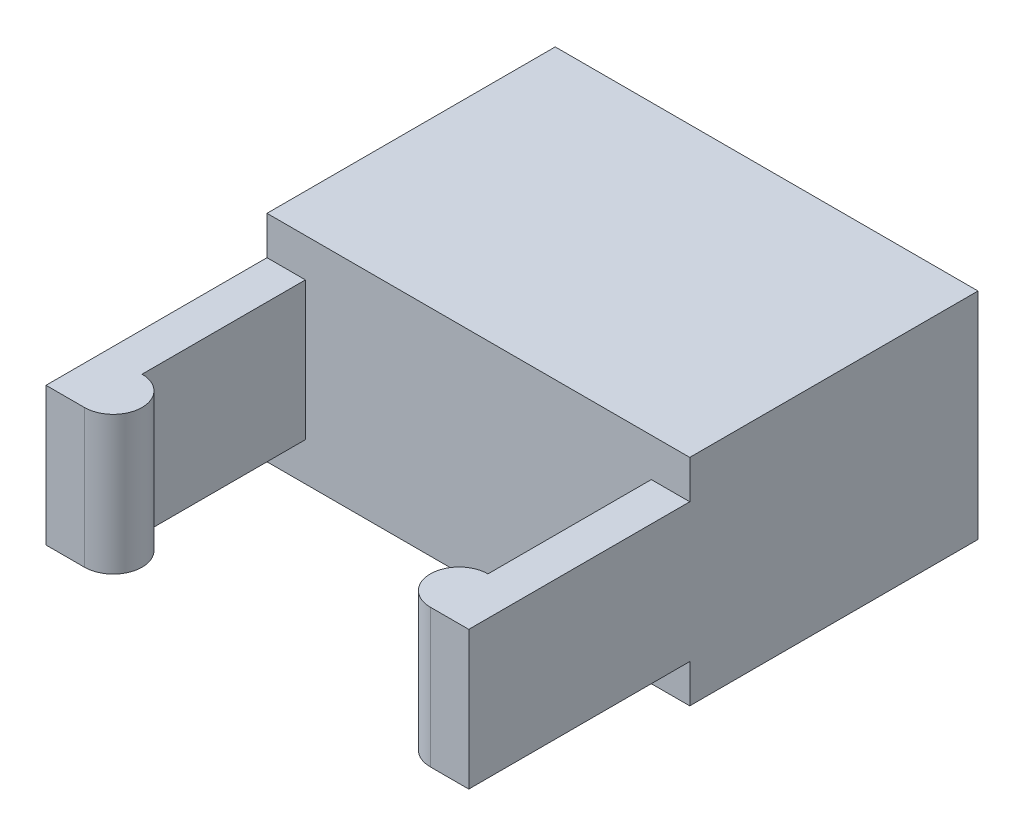
SolidWorks part; units mm, degrees
ref_plane "Front Plane" through (0, 0, 0) normal (0, 0, 1) x (1, 0, 0)
ref_plane "Top Plane" through (0, 0, 0) normal (0, 1, 0) x (1, 0, 0)
ref_plane "Right Plane" through (0, 0, 0) normal (1, 0, 0) x (0, 0, -1)
sketch "Sketch1" plane through (0, 0, 0) normal (0, 0, 1) x (1, 0, 0)
  line L1 (-9, 3.6) -> (9, 3.6)
  line L2 (-9, 3.6) -> (-9, -3.6)
  line L3 (-9, -3.6) -> (9, -3.6)
  line L4 (9, 3.6) -> (9, -3.6)
  line L5 (-9, 3.6) -> (9, -3.6) construction
  line L6 (-9, -3.6) -> (9, 3.6) construction
  line L11 (-5.6882, -3.6) -> (5.6882, 3.6) construction
  line L12 (-5.6882, 3.6) -> (5.6882, -3.6) construction
  line L13 (9, 3.6) -> (11, 3.6)
  line L14 (9, 3.6) -> (9, -3.6)
  line L15 (9, -3.6) -> (11, -3.6)
  line L16 (11, 3.6) -> (11, -3.6)
  line L17 (-9, 3.6) -> (-11, 3.6)
  line L18 (-9, 3.6) -> (-9, -3.6)
  line L19 (-9, -3.6) -> (-11, -3.6)
  line L20 (-11, 3.6) -> (-11, -3.6)
  line L21 (-11, 3.6) -> (11, 3.6)
  line L22 (-11, 3.6) -> (-11, 5.6)
  line L23 (-11, 5.6) -> (11, 5.6)
  line L24 (11, 3.6) -> (11, 5.6)
  line L25 (-11, -3.6) -> (11, -3.6)
  line L26 (-11, -3.6) -> (-11, -5.6)
  line L27 (-11, -5.6) -> (11, -5.6)
  line L28 (11, -3.6) -> (11, -5.6)
  point P0 (0, 0)
  point P6 (0, 0)
  dimension "D1" = 18
  dimension "D2" = 7.2
  dimension "D3" = 2
  dimension "D4" = 2
  dimension "D5" = 2
extrude "Boss-Extrude3" add sketch "Sketch1" along normal blind 15 contours L13 L24 L23 L22 L17 L1 | L17 L20 L19 L2 | L4 L1 L2 L3 | L28 L15 L3 L19 L26 L27 | L16 L13 L4 L15 region at (0, 4.6, 0) region at (0, 0, 0) region at (-10, 0, 0) region at (10, 0, 0) region at (0, -4.6, 0)
extrude "Boss-Extrude4" add sketch "Sketch1<4>" along normal blind 8.5 from surface contours L17 L20 L19 L2 | L16 L13 L4 L15 region at (-10, 0, 0) region at (10, 0, 0) starting at face at (0, 0, 15)
sketch "Sketch1<4>" plane through (0, 0, 0) normal (0, 0, 1) x (1, 0, 0) same geometry as "Sketch1"
sketch "Sketch3" plane through (0, 0, 0) normal (0, 1, 0) x (1, 0, 0)
  line L1 (-9, -23.5) -> (-9, -26.5) construction
  line L2 (-11, -23.5) -> (-9, -23.5)
  line L3 (-11, -23.5) -> (-11, -26.5)
  line L4 (-11, -26.5) -> (-9, -26.5)
  line L5 (-9, -23.5) -> (-9, -26.5)
  arc A0 (-9, -26.5) -> (-9, -23.5) centre (-9, -25) ccw
  dimension "D1" = 3
extrude "Boss-Extrude5" add sketch "Sketch3" along normal up to surface (3.6 mm away) from surface contours L5 L2 L3 L4 | L5 A0 region at (-10, 0, 25) region at (-8.3634, 0, 25) up to face at (-10, 3.6, 19.25) starting at face at (-10, -3.6, 19.25)
mirror "Mirror1" about plane through (0, 0, 0) normal (1, 0, 0) of "Boss-Extrude5"
